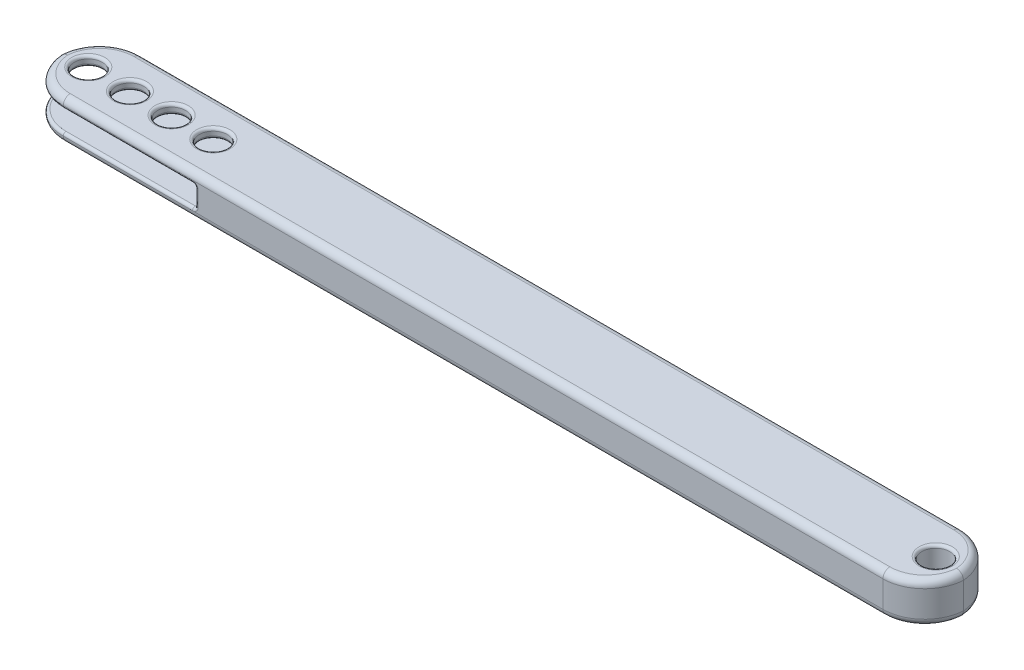
SolidWorks part; units mm, degrees
ref_plane "Front Plane" through (0, 0, 0) normal (0, 0, 1) x (1, 0, 0)
ref_plane "Top Plane" through (0, 0, 0) normal (0, 1, 0) x (1, 0, 0)
ref_plane "Right Plane" through (0, 0, 0) normal (1, 0, 0) x (0, 0, -1)
sketch "Sketch1" plane through (0, 0, 0) normal (0, 1, 0) x (1, 0, 0)
  line L1 (0, 0) -> (130, 0)
  line L2 (0, 0) -> (0, 11.2)
  line L3 (0, 11.2) -> (130, 11.2)
  line L4 (130, 0) -> (130, 11.2)
  line L5 (0, 0) -> (130, 11.2) construction
  line L6 (0, 11.2) -> (130, 0) construction
  point P4 (65, 5.6)
  dimension "D1" = 130
  dimension "D2" = 11.2
extrude "Boss-Extrude1" add sketch "Sketch1" along normal blind 5.8
sketch "Sketch2" plane through (0, 5.8, 0) normal (0, 1, 0) x (1, 0, 0)
  line L0 (0, 5.6) -> (130, 5.6) construction
  line L1 (0, 11.2) -> (0, 0) construction
  line L2 (130, 0) -> (130, 11.2) construction
  circle A0 centre (4, 5.6) radius 2
  circle A1 centre (126, 5.6) radius 2
  circle A2 centre (10, 5.6) radius 2
  circle A3 centre (16, 5.6) radius 2
  circle A4 centre (22, 5.6) radius 2
  dimension "D1" = 4
  dimension "D2" = 4
  dimension "D3" = 4
  dimension "D4" = 4
  dimension "D5" = 4
extrude "Cut-Extrude1" cut sketch "Sketch2" against normal through all
fillet "Fillet1" radius 6 4 edges at (130, 2.9, 0) (130, 2.9, -11.2) (0, 2.9, -11.2) (0, 2.9, 0)
fillet "Fillet2" radius 1 12 edges at (1.9012, 0, -1.6182) (128.0988, 0, -1.6182) (1.9012, 5.8, -1.6182) (128.0988, 5.8, -1.6182) (128.0988, 5.8, -9.5818) (1.9012, 5.8, -9.5818) (128.0988, 0, -9.5818) (1.9012, 0, -9.5818) (65, 0, 0) (65, 5.8, 0) (65, 5.8, -11.2) (65, 0, -11.2)
sketch "Sketch3" plane through (0, 0, -11.2) normal (0, 0, -1) x (-1, 0, 0)
  line L0 (-0.0133, 2.9) -> (-110.1882, 2.9) construction
  line L1 (-0.0133, 1) -> (-0.0133, 4.8) construction
  line L3 (-0.0133, 1.4) -> (-25.0133, 1.4)
  line L4 (-0.0133, 1.4) -> (-0.0133, 4.4)
  line L5 (-0.0133, 4.4) -> (-25.0133, 4.4)
  line L6 (-25.0133, 1.4) -> (-25.0133, 4.4)
  line L7 (-0.0133, 1.4) -> (-25.0133, 4.4) construction
  line L8 (-0.0133, 4.4) -> (-25.0133, 1.4) construction
  point P8 (-12.5133, 2.9)
  dimension "D1" = 25
  dimension "D2" = 3
extrude "Cut-Extrude2" cut sketch "Sketch3" against normal through all
fillet "Fillet3" radius 0.4 30 edges at (1.9012, 4.4, -1.6182) (1.9012, 4.4, -9.5818) (1.9012, 1.4, -1.6182) (1.9012, 1.4, -9.5818) (15.5067, 4.4, 0) (15.5067, 4.4, -11.2) (15.5067, 1.4, 0) (15.5067, 1.4, -11.2) (126, 5.8, -3.6) (126, 0, -3.6) (4, 5.8, -3.6) (2, 4.4, -5.6) (4, 0, -3.6) (6, 1.4, -5.6) (25.0133, 4.4, -5.6) (25.0133, 2.9, 0) (25.0133, 1.4, -5.6) (25.0133, 2.9, -11.2) (22, 0, -3.6) (24, 1.4, -5.6) (22, 5.8, -3.6) (20, 4.4, -5.6) (16, 0, -3.6) (18, 1.4, -5.6) (16, 5.8, -3.6) (14, 4.4, -5.6) (10, 0, -3.6) (12, 1.4, -5.6) (10, 5.8, -3.6) (8, 4.4, -5.6)
